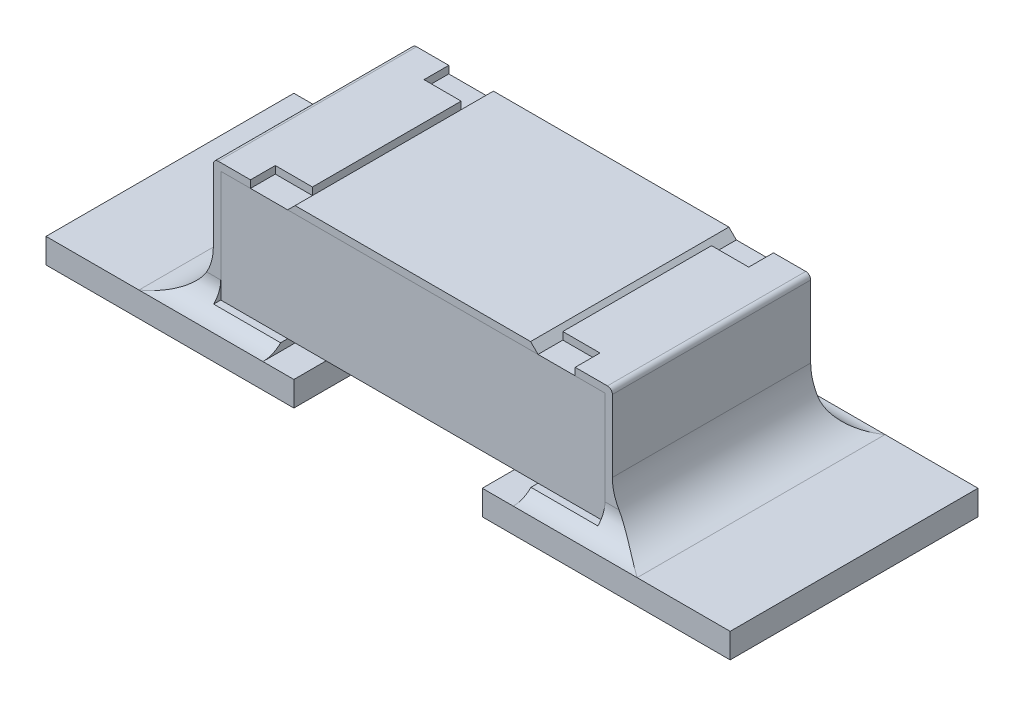
SolidWorks part; units mm, degrees
ref_plane "Front Plane" through (0, 0, 0) normal (0, 0, 1) x (1, 0, 0)
ref_plane "Top Plane" through (0, 0, 0) normal (0, 1, 0) x (1, 0, 0)
ref_plane "Right Plane" through (0, 0, 0) normal (1, 0, 0) x (0, 0, -1)
sketch "Sketch1" plane through (0, 0, 0) normal (1, 0, 0) x (0, 0, -1)
  line L1 (-0.4, 0.58) -> (0.4, 0.58)
  line L2 (-0.4, 0.58) -> (-0.4, 0.13)
  line L3 (-0.4, 0.13) -> (0.4, 0.13)
  line L4 (0.4, 0.58) -> (0.4, 0.13)
  line L5 (-0.4, 0.58) -> (0.4, 0.13) construction
  line L6 (-0.4, 0.13) -> (0.4, 0.58) construction
  point P0 (0, 0.355)
  point P5 (0, 0)
  dimension "D1" = 0.45
  dimension "D2" = 0.8
  dimension "D3" = 0.13
extrude "Boss-Extrude1" add sketch "Sketch1" along normal mid plane 1.55
sketch "Sketch2" plane through (0, 0, 0) normal (0, 0, 1) x (1, 0, 0)
  line L0 (-0.505, 0.58) -> (-0.775, 0.58)
  line L1 (-0.775, 0.58) -> (-0.775, 0.13)
  line L2 (-0.775, 0.13) -> (-0.505, 0.13)
  line L3 (-0.775, 0.58) -> (-0.775, 0.13) construction
  line L4 (0.775, 0.13) -> (-0.775, 0.13) construction
  line L5 (0.775, 0.58) -> (-0.775, 0.58) construction
  line L6 (-0.505, 0.61) -> (-0.805, 0.61)
  line L7 (-0.805, 0.61) -> (-0.805, 0.1)
  line L8 (-0.805, 0.1) -> (-0.505, 0.1)
  line L9 (-0.505, 0.61) -> (-0.505, 0.58)
  line L10 (-0.505, 0.13) -> (-0.505, 0.1)
  dimension "D1" = 0.03
  dimension "D2" = 0.3
extrude "Boss-Extrude2" add sketch "Sketch2" along normal mid plane 0.8 separate body
fillet "Fillet1" radius 0.02 1 edges at (-0.805, 0.61, 0)
sketch "Sketch3" plane through (0, 0.61, 0) normal (0, 1, 0) x (1, 0, 0)
  line L0 (-0.505, -0.4) -> (-0.785, -0.4) construction
  line L1 (-0.655, 0.3) -> (-0.505, 0.3)
  line L2 (-0.655, 0.3) -> (-0.655, 0.4)
  line L3 (-0.655, 0.4) -> (-0.505, 0.4)
  line L4 (-0.505, 0.3) -> (-0.505, 0.4)
  line L5 (-0.655, 0.3) -> (-0.505, 0.4) construction
  line L6 (-0.655, 0.4) -> (-0.505, 0.3) construction
  line L7 (-0.505, -0.4) -> (-0.655, -0.4)
  line L8 (-0.505, -0.4) -> (-0.505, -0.3)
  line L9 (-0.505, -0.3) -> (-0.655, -0.3)
  line L10 (-0.655, -0.4) -> (-0.655, -0.3)
  line L11 (-0.505, -0.4) -> (-0.655, -0.3) construction
  line L12 (-0.505, -0.3) -> (-0.655, -0.4) construction
  line L13 (-0.505, -0.4) -> (-0.505, 0.4) construction
  line L14 (-0.505, 0.4) -> (-0.785, 0.4) construction
  point P0 (-0.58, 0.35)
  point P5 (-0.58, -0.35)
  dimension "D1" = 0.15
  dimension "D2" = 0.1
extrude "Cut-Extrude1" cut sketch "Sketch3" against normal blind 0.03
sketch "Sketch6" plane through (0, 0.1, 0) normal (0, -1, 0) x (1, 0, 0)
  line L1 (-1.38, 0.5) -> (-0.38, 0.5)
  line L2 (-1.38, 0.5) -> (-1.38, -0.5)
  line L3 (-1.38, -0.5) -> (-0.38, -0.5)
  line L4 (-0.38, 0.5) -> (-0.38, -0.5)
  line L5 (-1.38, 0.5) -> (-0.38, -0.5) construction
  line L6 (-1.38, -0.5) -> (-0.38, 0.5) construction
  point P0 (-0.88, 0)
  point P5 (0, 0)
  point P6 (0, 0)
  dimension "D1" = 1
  dimension "D2" = 0.38
extrude "Boss-Extrude5" add sketch "Sketch6" along normal blind 0.1
fillet "Fillet2" radius 0.2 1 edges at (-0.805, 0.1, 0)
fillet "Fillet3" radius 0.1 2 edges at (-0.755, 0.1, -0.4) (-0.755, 0.1, 0.4)
mirror "Mirror2" about plane through (0, 0, 0) normal (1, 0, 0) of bodies 107
sketch "Sketch7" plane through (0, 0, 0.4) normal (0, 0, 1) x (1, 0, 0)
  line L0 (-0.505, 0.58) -> (0.505, 0.58)
  line L1 (0.505, 0.58) -> (0.475, 0.61)
  line L2 (0.475, 0.61) -> (-0.475, 0.61)
  line L3 (-0.475, 0.61) -> (-0.505, 0.58)
  line L4 (0.775, 0.58) -> (-0.775, 0.58) construction
  line L5 (0.505, 0.58) -> (0.505, 0.61) construction
  line L6 (-0.505, 0.58) -> (-0.505, 0.61) construction
  point P2 (0, 0)
  point P7 (0, 0)
  point P10 (0, 0)
  dimension "D1" = 45
  dimension "D2" = 45
  dimension "D3" = 0.03
extrude "Boss-Extrude6" add sketch "Sketch7" against normal up to surface (0.8 mm away) separate body up to face at (0, 0.355, -0.4)
